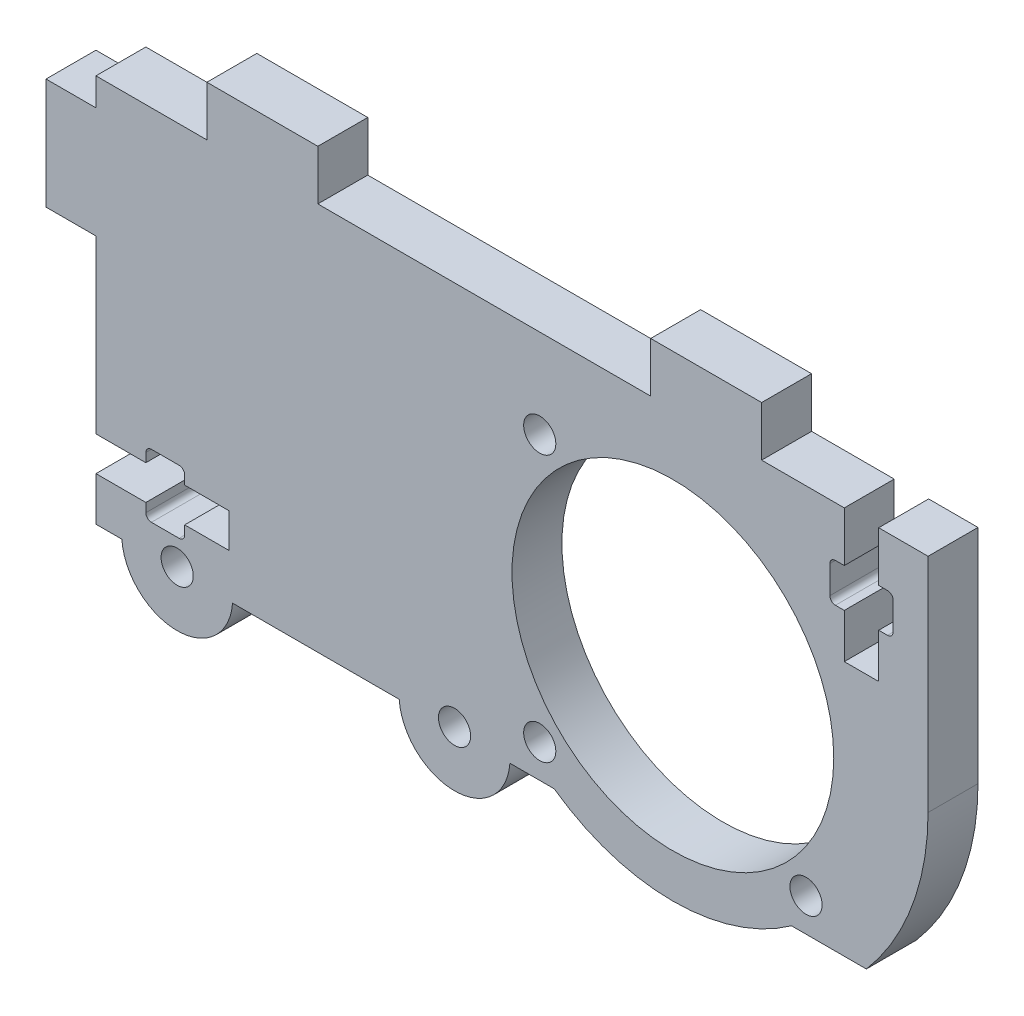
SolidWorks part; units mm, degrees
ref_plane "Front Plane" through (0, 0, 0) normal (0, 0, 1) x (1, 0, 0)
ref_plane "Top Plane" through (0, 0, 0) normal (0, 1, 0) x (1, 0, 0)
ref_plane "Right Plane" through (0, 0, 0) normal (1, 0, 0) x (0, 0, -1)
sketch "Sketch1" plane through (0, 0, 0) normal (0, 0, 1) x (1, 0, 0)
  line L0 (0, 0) -> (0, -35)
  line L1 (0, -35) -> (75, -35)
  line L2 (75, -35) -> (75, 0)
  line L3 (75, 0) -> (0, 0)
  dimension "D1" = 75
  dimension "D2" = 35
extrude "MainShape" add sketch "Sketch1" along normal blind 4.5
sketch "Sketch2" plane through (0, 0, 4.5) normal (0, 0, 1) x (1, 0, 0)
  line L0 (0, -2.5) -> (-4.5, -2.5)
  line L1 (0, 0) -> (0, -35) construction
  line L2 (-4.5, -2.5) -> (-4.5, -12.5)
  line L3 (-4.5, -12.5) -> (0, -12.5)
  line L4 (0, -12.5) -> (0, -2.5)
  line L5 (-4.5, -7.5) -> (0, -7.5) construction
  dimension "D1" = 10
  dimension "D2" = 4.5
  dimension "D3" = 7.5
extrude "RearTab" add sketch "Sketch2" against normal through all
sketch "Sketch3" plane through (0, 0, 4.5) normal (0, 0, 1) x (1, 0, 0)
  line L0 (75, 0) -> (0, 0) construction
  line L1 (10, 0) -> (20, 0)
  line L2 (10, 0) -> (10, 4.5)
  line L3 (10, 4.5) -> (20, 4.5)
  line L4 (20, 0) -> (20, 4.5)
  line L5 (15, 4.5) -> (15, 0) construction
  line L6 (50, 0) -> (60, 0)
  line L7 (50, 0) -> (50, 4.5)
  line L8 (50, 4.5) -> (60, 4.5)
  line L9 (60, 0) -> (60, 4.5)
  line L10 (55, 4.5) -> (55, 0) construction
  dimension "D1" = 4.5
  dimension "D2" = 10
  dimension "D3" = 40
  dimension "D4" = 15
extrude "Boss-Extrude3" add sketch "Sketch3" against normal through all
sketch "Sketch4" plane through (0, 0, 4.5) normal (0, 0, 1) x (1, 0, 0)
  line L0 (69, 0) -> (69, -12) construction
  line L1 (75, 0) -> (60, 0) construction
  line L2 (70.55, -12) -> (67.45, -12) construction
  line L3 (67.45, -12) -> (67.45, 0) construction
  line L4 (67.45, 0) -> (67.45, -4.5)
  line L5 (67.45, -4.5) -> (66.65, -4.5)
  line L6 (66.15, -5) -> (66.15, -7.5)
  line L7 (66.65, -8) -> (67.45, -8)
  line L8 (67.45, -8) -> (67.45, -12)
  line L9 (67.45, -12) -> (70.55, -12)
  line L10 (67.45, 0) -> (70.55, 0)
  line L11 (70.55, -12) -> (70.55, 0) construction
  line L12 (70.55, -8) -> (70.55, -12)
  line L13 (71.35, -8) -> (70.55, -8)
  line L14 (71.85, -5) -> (71.85, -7.5)
  line L15 (70.55, -4.5) -> (71.35, -4.5)
  line L16 (70.55, 0) -> (70.55, -4.5)
  arc A0 (66.15, -7.5) -> (66.65, -8) centre (66.65, -7.5) ccw
  arc A1 (66.65, -4.5) -> (66.15, -5) centre (66.65, -5) ccw
  arc A2 (71.35, -4.5) -> (71.85, -5) centre (71.35, -5) cw
  arc A3 (71.85, -7.5) -> (71.35, -8) centre (71.35, -7.5) cw
  point P13 (66.15, -8)
  point P16 (66.15, -4.5)
  point P27 (71.85, -4.5)
  point P28 (71.85, -8)
  dimension "D7" = 0.5
  dimension "D1" = 12
  dimension "D2" = 1.55
  dimension "D3" = 3.5
  dimension "D4" = 2.85
  dimension "D5" = 8
  dimension "D6" = 69
extrude "Cut-Extrude1" cut sketch "Sketch4" against normal through all
sketch "Sketch5" plane through (0, 0, 4.5) normal (0, 0, 1) x (1, 0, 0)
  line L0 (45.0208, 0) -> (45.0208, 4.5) construction
  line L1 (42.5416, 0) -> (47.5, 0)
  line L2 (42.5416, 0) -> (42.5416, -5.18)
  line L3 (42.5416, -5.18) -> (47.5, -5.18)
  line L4 (47.5, 0) -> (47.5, -5.18)
  line L5 (42.5416, 0) -> (47.5, -5.18) construction
  line L6 (42.5416, -5.18) -> (47.5, 0) construction
  line L7 (42, -4.18) -> (48, -4.18) construction
  line L8 (50, 0) -> (20, 0) construction
  line L9 (48, -4.18) -> (48, -1.18) construction
  line L10 (48, -2.68) -> (58, -2.68) construction
  line L11 (48, -4.18) -> (48, -1.18) construction
  line L12 (58, -1.18) -> (58, -4.18) construction
  line L13 (53, -2.68) -> (53, 0) construction
  line L14 (0, 0) -> (19.5, 0) construction
  line L15 (63.4584, -5.18) -> (58.5, 0) construction
  line L16 (63.4584, 0) -> (58.5, -5.18) construction
  line L17 (58.5, 0) -> (58.5, -5.18)
  line L18 (63.4584, -5.18) -> (58.5, -5.18)
  line L19 (63.4584, 0) -> (63.4584, -5.18)
  line L20 (63.4584, 0) -> (58.5, 0)
  line L21 (42.5416, -5.18) -> (47.5, 0) construction
  point P0 (45.0208, -2.59)
  point P27 (60.9792, -2.59)
  dimension "D1" = 1
  dimension "D2" = 0
  dimension "D3" = 0.5
extrude "Cut-Extrude2" [suppressed] cut sketch "Sketch5" against normal through all
sketch "Sketch6" plane through (0, 0, 4.5) normal (0, 0, 1) x (1, 0, 0)
  line L0 (52, -20) -> (40, -8) construction
  line L2 (52, -34.5) -> (52, -5.5) construction
  line L3 (52, -20) -> (37.5, -20) construction
  line L4 (52, -20) -> (64, -8) construction
  line L5 (52, -20) -> (64, -32) construction
  line L6 (52, -20) -> (40, -32) construction
  circle A0 centre (52, -20) radius 14.5
  circle A1 centre (40, -8) radius 1.45
  circle A3 centre (64, -32) radius 1.45
  circle A4 centre (40, -32) radius 1.45
  dimension "D1" = 29
  dimension "D4" = 2.9
  dimension "D2" = 52
  dimension "D3" = 20
  dimension "D5" = 12
  dimension "D6" = 45
extrude "Cut-Extrude3" cut sketch "Sketch6" against normal through all
sketch "Sketch7" plane through (0, 0, 4.5) normal (0, 0, 1) x (1, 0, 0)
  line L0 (0, -35) -> (62.6919, -35)
  arc A0 (41.3081, -35) -> (62.6919, -35) centre (52, -20) ccw
  circle A1 centre (52, -20) radius 14.5 construction
  circle A2 centre (64, -32) radius 1.45 construction
extrude "Boss-Extrude4" add sketch "Sketch7" against normal through all contours L0 A0 region at (52, -36.3797, 4.5)
sketch "Sketch8" [suppressed] plane through (0, 0, 4.5) normal (0, 0, 1) x (1, 0, 0)
  line L1 (0, -35) -> (39.1367, -35) construction
  line L18 (15, -35) -> (15, -9.316) construction
  line L19 (6.3379, -28.8128) -> (15, -37.4749) construction
  line L20 (8.8128, -26.3379) -> (17.4749, -35) construction
  line L21 (6.3379, -28.8128) -> (8.8128, -26.3379) construction
  line L22 (15, -35) -> (7.5754, -27.5754) construction
  line L23 (15, -37.4749) -> (11.0756, -33.5504)
  line L24 (11.0756, -33.5504) -> (10.1917, -34.4343)
  line L25 (10.1917, -34.4343) -> (7.2218, -31.4645)
  line L26 (7.2218, -31.4645) -> (8.1057, -30.5806)
  line L27 (8.1057, -30.5806) -> (6.3379, -28.8128)
  line L28 (15, -37.4749) -> (15, -35)
  line L29 (17.4749, -35) -> (15, -35)
  line L30 (8.8128, -26.3379) -> (6.3379, -28.8128)
  line L31 (10.5806, -28.1057) -> (8.8128, -26.3379)
  line L32 (11.4645, -27.2218) -> (10.5806, -28.1057)
  line L33 (14.4343, -30.1917) -> (11.4645, -27.2218)
  line L34 (13.5504, -31.0756) -> (14.4343, -30.1917)
  line L35 (17.4749, -35) -> (13.5504, -31.0756)
  dimension "D7" = 15
extrude "Cut-Extrude4" [suppressed] cut sketch "Sketch8" against normal through all
sketch "Sketch10" [suppressed] plane through (0, 0, 4.5) normal (0, 0, 1) x (1, 0, 0)
  line L0 (17.4749, -35) -> (21.7175, -30.7574)
  line L1 (21.7175, -30.7574) -> (25.253, -34.2929)
  line L2 (25.253, -34.2929) -> (24.5459, -35)
  line L3 (17.4749, -35) -> (39.1367, -35) construction
  line L4 (24.5459, -35) -> (17.4749, -35)
  line L5 (17.4749, -35) -> (13.5504, -31.0756) construction
  dimension "D1" = 5
  dimension "D2" = 6
extrude "Cut-Extrude6" [suppressed] cut sketch "Sketch10" against normal through all
sketch "Sketch12" plane through (0, 0, 4.5) normal (0, 0, 1) x (1, 0, 0)
  line L0 (7.3224, -34.6526) -> (32.3224, -34.6526) construction
  circle A0 centre (32.3224, -34.6526) radius 5
  circle A1 centre (7.3224, -34.6526) radius 5
  dimension "D1" = 10
  dimension "D2" = 10
  dimension "D3" = 25
  dimension "D4" = 34.6526
  dimension "D5" = 7.3224
extrude "Boss-Extrude5" add sketch "Sketch12" against normal through all
sketch "Sketch11" plane through (0, 0, 4.5) normal (0, 0, 1) x (1, 0, 0)
  line L0 (0, -29.5) -> (12, -29.5) construction
  line L1 (0, -12.5) -> (0, -35) construction
  line L2 (12, -31.05) -> (12, -27.95) construction
  line L3 (12, -27.95) -> (0, -27.95) construction
  line L4 (0, -31.05) -> (0, -27.95)
  line L5 (0, -27.95) -> (4.5, -27.95)
  line L6 (4.5, -27.95) -> (4.5, -27.15)
  line L7 (5, -26.65) -> (7.5, -26.65)
  line L8 (8, -27.15) -> (8, -27.95)
  line L9 (8, -27.95) -> (12, -27.95)
  line L10 (12, -27.95) -> (12, -31.05)
  line L11 (12, -31.05) -> (0, -31.05) construction
  line L12 (8, -31.05) -> (12, -31.05)
  line L13 (8, -31.85) -> (8, -31.05)
  line L14 (5, -32.35) -> (7.5, -32.35)
  line L15 (4.5, -31.05) -> (4.5, -31.85)
  line L16 (0, -31.05) -> (4.5, -31.05)
  line L17 (-4.5, -2.5) -> (-4.5, -12.5) construction
  arc A0 (7.5, -26.65) -> (8, -27.15) centre (7.5, -27.15) cw
  arc A1 (4.5, -27.15) -> (5, -26.65) centre (5, -27.15) cw
  arc A2 (4.5, -31.85) -> (5, -32.35) centre (5, -31.85) ccw
  arc A3 (7.5, -32.35) -> (8, -31.85) centre (7.5, -31.85) ccw
  point P12 (8, -26.65)
  point P15 (4.5, -26.65)
  point P26 (4.5, -32.35)
  point P27 (8, -32.35)
  point P28 (-4.5, -7.5)
  dimension "D1" = 12
  dimension "D2" = 1.55
  dimension "D3" = 3.5
  dimension "D4" = 2.85
  dimension "D5" = 8
  dimension "D6" = 0.5
  dimension "D7" = 22
extrude "Cut-Extrude7" cut sketch "Sketch11" against normal through all
sketch "Sketch13" plane through (0, 0, 4.5) normal (0, 0, 1) x (1, 0, 0)
  circle A0 centre (7.3224, -34.6526) radius 1.45
  circle A1 centre (32.3224, -34.6526) radius 1.45
  arc A2 (2.3345, -35) -> (12.3103, -35) centre (7.3224, -34.6526) ccw construction
  arc A3 (27.3345, -35) -> (37.3103, -35) centre (32.3224, -34.6526) ccw construction
  dimension "D1" = 2.9
extrude "Cut-Extrude8" cut sketch "Sketch13" against normal through all
sketch "Sketch14" plane through (0, 0, 4.5) normal (0, 0, 1) x (1, 0, 0)
  line L0 (75, -35) -> (75, 0) construction
  line L1 (69.4356, -35) -> (75, -35)
  line L2 (75, -35) -> (75, -20)
  arc A0 (69.4356, -35) -> (75, -20) centre (52, -20) ccw
  circle A1 centre (52, -20) radius 14.5 construction
extrude "SmoothEdge" cut sketch "Sketch14" against normal through all
equation "\"X-ROD-SPACING\"=45"
equation "\"Y-ROD-SPACING\"=75"
equation "\"Z-ROD-SPACING\"=17.5"
equation "\"Y-BED-OFFSET\"=2"
equation "\"Y-BED-ROD-INSET\"=3.5"
equation "\"Y-BED-SCREW-SPACING\"=209"
equation "\"Y-BED-SCREW-CUTOUT-SLOT-HEIGHT\"=2"
equation "\"T-SLOT-NUT-FILLET-RADIUS\"=0.5"
equation "\"T-SLOT-SCREW-SHAFT-RADIUS\"=1.55"
equation "\"T-SLOT-SCREW-SHAFT-CUTOUT-LENGTH\"=11.0"
equation "\"T-SLOT-NUT-DEPTH\"=3.5"
equation "\"T-SLOT-NUT-WIDTH\"=2.85"
equation "\"T-SLOT-NUT-END-DISTANCE\"=8"
equation "\"ACRYLIC-THICKNESS\"=10"
equation "\"ACRYLIC-THICKNESS2\"=4.5"
equation "\"ACRYLIC-TAB-CUTOUT-SIZE\"=\"ACRYLIC-THICKNESS\"+\"ACRYLIC-TAB-TOLERANCE\"*2"
equation "\"ACRYLIC-TAB-TOLERANCE\"=-.05"
equation "\"ACRYLIC-TAB-WIDTH\"=\"ACRYLIC-THICKNESS\""
equation "\"ACRYLIC-M3-HOLE\"=2.9"
equation "\"SMOOTHROD-CAP-SCREW-DISTANCE\"=20"
equation "\"FRAME-WIDTH-INNER\"=370"
equation "\"NEMA17-HOLE-SPACING\"=31"
equation "\"NEMA17-CENTRAL-CUTOUT\"=22.5"
equation "\"Z-BRACKET-REACH\"=55"
equation "\"Z-ROD-INSET\"=16"
equation "\"TOP-BRACKET-SPACING\"=40"
equation "\"SMOOTHROD-X-LENGTH\"=350"
equation "\"SMOOTHROD-Y-LENGTH\"=350"
equation "\"SMOOTHROD-Z-LENGTH\"=350"
equation "\"SMOOTHROD-TIGHTENING-HEADROOM\"=.25"
equation "\"LEADSCREW-Z-LENGTH\"=300"
equation "\"SCREW-LENGTH-FRAME\"=\"ACRYLIC-THICKNESS\" + 10"
equation "\"SCREW-LENGTH-MOTOR\"=\"ACRYLIC-THICKNESS\" + 5"
equation "\"SCREW-LENGTH-EXTRUDER\"=28"
equation "\"SCREW-HEAD-RADIUS\"=6"
equation "\"PRINTED-M3-HOLE\"=3.5"
equation "\"PRINTED-X-SMOOTHROD-DIAMETER\"=9.0"
equation "\"PRINTED-X-SMOOTHROD-CUTOUT\"=10"
equation "\"PRINTED-X-BASE-HEIGHT\"=10"
equation "\"PRINTED-LM8UU-CUTOUT-SIZE\"=15.5"
equation "\"PRINTED-LM8UU-CUTOUT-LENGTH\"=24.5"
equation "\"PRINTED-X-IDLER-HEIGHT\"=16"
equation "\"PRINTED-M3-NUT-AF\"=6.25"
equation "\"PSU-MOUNTING-WIDTH\"=95"
equation "\"PSU-MOUNTING-HEIGHT\"=177"
equation "\"Y-BELT-TO-ROD-DISTANCE\"=20"
equation "\"SPOOL-HOLDER-ROD-SPACING\"=150"
equation "\"ACRYLIC-X-CARRIAGE-WIDTH\"=55"
equation "\"ACRYLIC-X-CARRIAGE-HEIGHT\"=75"
equation "\"ACRYLIC-X-CARRIAGE-LM8UU-CUTOUT-WIDTH\"=24.25"
equation "\"ACRYLIC-X-CARRIAGE-LM8UU-CUTOUT-HEIGHT\"=11.0"
equation "\"ACRYLIC-X-CARRIAGE-SCREW-SPACING-X\"=15"
equation "\"ACRYLIC-X-CARRIAGE-SCREW-SPACING-Y\"=33"
equation "\"ACRYLIC-X-CARRIAGE-CENTER-TAB-SPACING\"=14"
equation "\"ACRYLIC-X-CARRIAGE-EXTRUDER-OFFSET\"=26"
equation "\"ACRYLIC-X-CARRIAGE-EXTRUDER-ANGLE\"=90"
equation "\"ACRYLIC-X-CARRIAGE-EXTRUDER-SHELF-DEPTH\"=\"ACRYLIC-X-CARRIAGE-EXTRUDER-OFFSET\" + 28"
equation "\"ACRYLIC-X-CARRIAGE-EXTRUDER-BRACE-SPACING\"=23"
equation "\"ACRYLIC-X-CARRIAGE-EXTRUDER-BRACE-TAB-OFFSET\"=20"
equation "\"ACRYLIC-X-CARRIAGE-EXTRUDER-BRACE-HEIGHT\"=35"
equation "\"ACRYLIC-X-CARRIAGE-EXTRUDER-BRACE-SCREW-SPACING\"=22"
equation "\"ACRYLIC-X-CARRIAGE-DUAL-WIDTH-MULTIPLIER\"=1.65"
equation "\"ACRYLIC-X-CARRIAGE-DUAL-HOTEND-SPACING\"=42"
equation "\"ACRYLIC-X-CARRIAGE-DUAL-WIDTH\"=75"
equation "\"ACRYLIC-X-CARRIAGE-DUAL-FAN-OFFSET\"=52"
equation "\"ACRYLIC-X-CARRIAGE-DUAL-FAN-HEIGHT\"=20"
equation "\"ACRYLIC-X-CARRIAGE-DUAL-HOTEND-SEPARATION\"=36"
equation "\"ACRYLIC-X-CARRIAGE-DUAL-MOUNT-PLATE-DEPTH\"=75"
equation "\"ACRYLIC-X-CARRIAGE-DUAL-MOUNT-BRACE-WIDTH\"=33"
equation "\"ACRYLIC-X-CARRIAGE-DUAL-MOUNT-SCREW-WIDTH\"=40"
equation "\"BLOWER-FAN-WIDTH\"=15"
equation "\"D1@Sketch1\"=\"ACRYLIC-X-CARRIAGE-DUAL-MOUNT-PLATE-DEPTH\""
equation "\"D2@Sketch1\"=\"ACRYLIC-X-CARRIAGE-EXTRUDER-BRACE-HEIGHT\""
equation "\"D1@MainShape\" = \"ACRYLIC-THICKNESS2\""
equation "\"D1@Sketch2\"=\"ACRYLIC-TAB-WIDTH\""
equation "\"D2@Sketch2\"=\"ACRYLIC-THICKNESS2\""
equation "\"D1@Sketch3\"=\"ACRYLIC-THICKNESS2\""
equation "\"D2@Sketch3\"=\"ACRYLIC-TAB-WIDTH\""
equation "\"D1@Sketch4\"=\"T-SLOT-SCREW-SHAFT-CUTOUT-LENGTH\"+1"
equation "\"D2@Sketch4\"=\"T-SLOT-SCREW-SHAFT-RADIUS\""
equation "\"D3@Sketch4\"=\"T-SLOT-NUT-DEPTH\""
equation "\"D4@Sketch4\"=\"T-SLOT-NUT-WIDTH\""
equation "\"D5@Sketch4\"=\"T-SLOT-NUT-END-DISTANCE\""
equation "\"D7@Sketch4\"=\"T-SLOT-NUT-FILLET-RADIUS\""
equation "\"D2@Sketch6\"=\"ACRYLIC-X-CARRIAGE-DUAL-FAN-OFFSET\""
equation "\"D3@Sketch6\"=\"ACRYLIC-X-CARRIAGE-DUAL-FAN-HEIGHT\""
equation "\"D4@Sketch6\"=\"ACRYLIC-M3-HOLE\""
equation "\"D1@Sketch11\"=\"T-SLOT-SCREW-SHAFT-CUTOUT-LENGTH\"+1"
equation "\"D2@Sketch11\"=\"T-SLOT-SCREW-SHAFT-RADIUS\""
equation "\"D3@Sketch11\"=\"T-SLOT-NUT-DEPTH\""
equation "\"D4@Sketch11\"=\"T-SLOT-NUT-WIDTH\""
equation "\"D5@Sketch11\"=\"T-SLOT-NUT-END-DISTANCE\""
equation "\"D6@Sketch11\"=\"T-SLOT-NUT-FILLET-RADIUS\""
equation "\"D1@Sketch13\"=\"ACRYLIC-M3-HOLE\""
